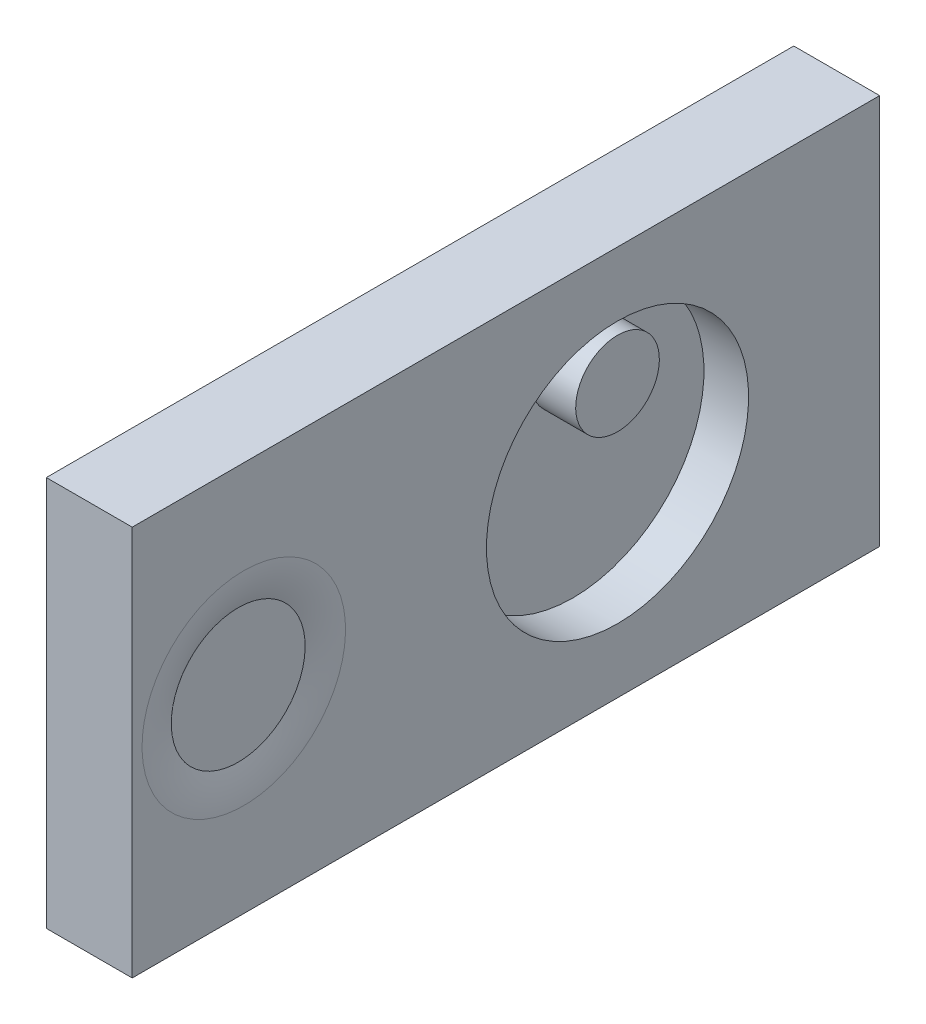
SolidWorks part; units mm, degrees
ref_plane "Front Plane" through (0, 0, 0) normal (0, 0, 1) x (1, 0, 0)
ref_plane "Top Plane" through (0, 0, 0) normal (0, 1, 0) x (1, 0, 0)
ref_plane "Right Plane" through (0, 0, 0) normal (1, 0, 0) x (0, 0, -1)
sketch "Sketch1" plane through (0, 0, 0) normal (0, 0, 1) x (1, 0, 0)
  line L1 (0, 0) -> (7.7, 0)
  line L2 (0, 0) -> (0, 35)
  line L3 (0, 35) -> (7.7, 35)
  line L4 (7.7, 0) -> (7.7, 35)
  dimension "D1" = 35
  dimension "D2" = 7.7
extrude "Boss-Extrude1" add sketch "Sketch1" against normal blind 47
sketch "Sketch2" plane through (7.7, 0, 0) normal (1, 0, 0) x (0, 0, -1)
  line L0 (47, 35) -> (0, 35) construction
  line L1 (0, 0) -> (0, 35) construction
  line L2 (9.9928, 28.15) -> (43.8191, 28.15) construction
  circle A0 centre (23.5, 17.5) radius 11.75
  circle A1 centre (23.5, 24.4) radius 3.75
  point P5 (23.5, 35)
  point P6 (23.5, 29.25)
  point P9 (0, 17.5)
  point P13 (0, 0)
  point P14 (0, 0)
  dimension "D1" = 23.5
  dimension "D2" = 7.5
  dimension "D3" = 1.1
extrude "Cut-Extrude1" cut sketch "Sketch2" against normal blind 4
sketch "Sketch3" plane through (0, 0, 0) normal (0, 0, 1) x (1, 0, 0)
  line L1 (0, 35) -> (7.7, 35)
  line L2 (0, 35) -> (0, 0)
  line L3 (0, 0) -> (7.7, 0)
  line L4 (7.7, 35) -> (7.7, 0)
extrude "Boss-Extrude2" add sketch "Sketch3" along normal blind 20
sketch "Sketch4" plane through (7.7, 0, 0) normal (1, 0, 0) x (0, 0, -1)
  line L0 (-20, 0) -> (-20, 35) construction
  line L1 (0, 0) -> (-20, 0) construction
  circle A0 centre (-10, 17.5) radius 6
  point P2 (-10, 0)
  point P5 (-20, 17.5)
  dimension "D1" = 12
extrude "Cut-Extrude2" cut sketch "Sketch4" against normal blind 0.5
fillet "Fillet1" radius 10 1 edges at (7.7, 23.5, 10)
